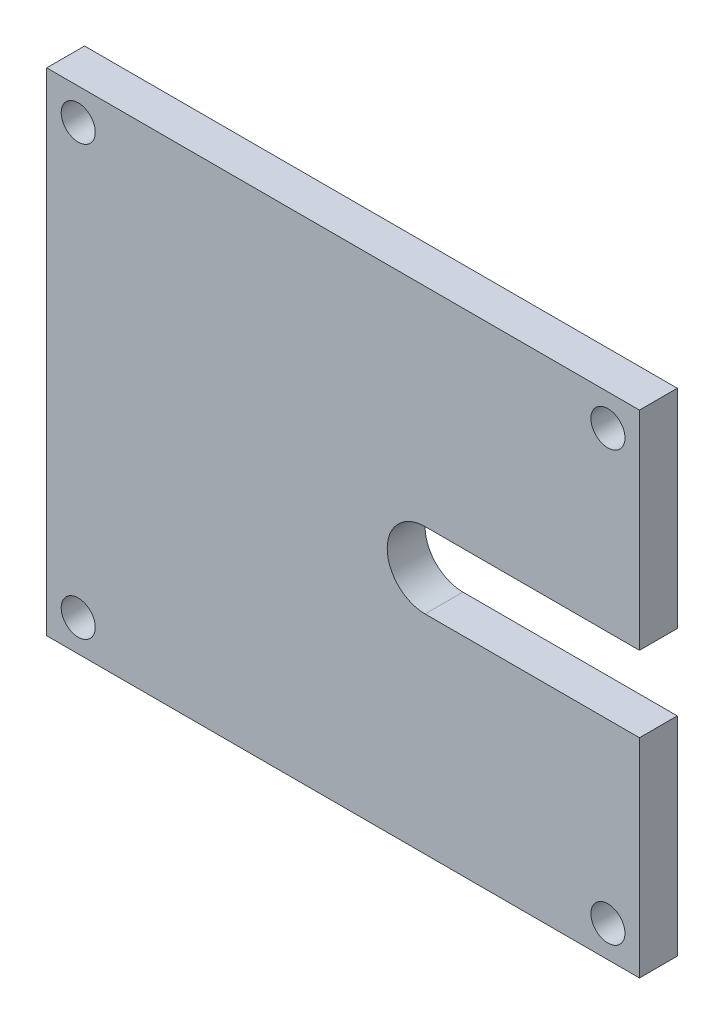
SolidWorks part; units mm, degrees
ref_plane "前视基准面" through (0, 0, 0) normal (0, 0, 1) x (1, 0, 0)
ref_plane "上视基准面" through (0, 0, 0) normal (0, 1, 0) x (1, 0, 0)
ref_plane "右视基准面" through (0, 0, 0) normal (1, 0, 0) x (0, 0, -1)
sketch "草图1" plane through (0, 0, 0) normal (0, 0, 1) x (1, 0, 0)
  line L1 (-23.5, -19.5) -> (23.5, -19.5)
  line L2 (-23.5, -19.5) -> (-23.5, 19.5)
  line L3 (-23.5, 19.5) -> (23.5, 19.5)
  line L4 (23.5, -19.5) -> (23.5, 19.5)
  line L5 (-23.5, -19.5) -> (23.5, 19.5) construction
  line L6 (-23.5, 19.5) -> (23.5, -19.5) construction
  point P0 (0, 0)
  dimension "D1" = 47
  dimension "D2" = 39
extrude "凸台-拉伸1" add sketch "草图1" along normal blind 3
sketch "草图2" plane through (0, 0, 3) normal (0, 0, 1) x (1, 0, 0)
  line L1 (-21, -17) -> (21, -17)
  line L2 (-21, -17) -> (-21, 17)
  line L3 (-21, 17) -> (21, 17)
  line L4 (21, -17) -> (21, 17)
  line L5 (-21, -17) -> (21, 17) construction
  line L6 (-21, 17) -> (21, -17) construction
  line L7 (0, 0) -> (21, 0) construction
  line L9 (0, 0) -> (0, 17) construction
  point P2 (21, 17)
  point P5 (-21, -17)
  point P6 (-21, 17)
  point P7 (21, -17)
  dimension "D1" = 42
  dimension "D2" = 34
hole_wizard "M2.5 间隙孔1" positions "草图4" profile "草图3" hole size "M2.5" standard "GB" end condition up to next
sketch "草图4" plane through (0, 0, 3) normal (0, 0, 1) x (1, 0, 0)
  point P0 (-21, -17)
  point P3 (21, 17)
  point P6 (21, -17)
  point P9 (-21, 17)
sketch "草图3" plane through (-21, -17, 3) normal (1, 0, 0) x (0, -1, 0)
  line L0 (0, 0) -> (0, 3)
  line L1 (0, 3) -> (1.35, 3)
  line L2 (1.35, 3) -> (1.35, 0)
  line L5 (1.35, 0) -> (0, 0)
  line L11 (0, -6.35) -> (0, 107.95) construction
  dimension "通孔孔直径" = 2.7
  dimension "通孔孔深度" = 3
sketch "草图5" plane through (0, 0, 3) normal (0, 0, 1) x (1, 0, 0)
  line L0 (6.5, 0) -> (23.5, 0) construction
  line L1 (23.5, -19.5) -> (23.5, 19.5) construction
  line L2 (6.5, 3) -> (23.5, 3)
  line L3 (6.5, -3) -> (23.5, -3)
  arc A0 (6.5, 3) -> (6.5, -3) centre (6.5, 0) ccw
  arc A1 (23.5, -3) -> (23.5, 3) centre (23.5, 0) ccw
  point P4 (15, 0)
  dimension "D2" = 20
  dimension "D1" = 6
extrude "切除-拉伸1" cut sketch "草图5" against normal up to next
